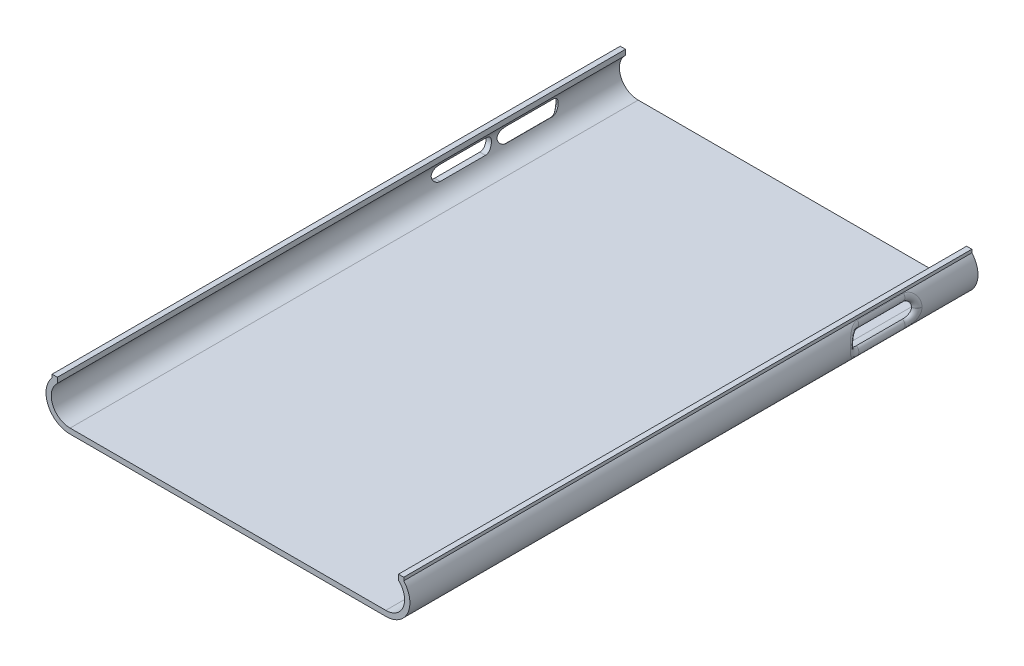
SolidWorks part; units mm, degrees
ref_plane "Front Plane" through (0, 0, 0) normal (0, 0, 1) x (1, 0, 0)
ref_plane "Top Plane" through (0, 0, 0) normal (0, 1, 0) x (1, 0, 0)
ref_plane "Right Plane" through (0, 0, 0) normal (1, 0, 0) x (0, 0, -1)
sketch "Sketch1" plane through (0, 0, 0) normal (0, 0, 1) x (1, 0, 0)
  line L0 (-30, -3.55) -> (30, -3.55)
  line L6 (-29.9932, -4.55) -> (29.9932, -4.55)
  line L13 (32.4171, 2.6) -> (32.4171, 3.6128)
  line L15 (0, 5.8259) -> (0, 4.6128) construction
  line L17 (33.4171, 3.012) -> (33.4171, 3.6128)
  line L19 (-33.4171, 3.012) -> (-33.4171, 3.6128)
  line L20 (-32.4171, 2.6) -> (-32.4171, 3.6128)
  line L21 (-32.4171, 3.6128) -> (-33.4171, 3.6128)
  line L22 (32.4171, 3.6128) -> (33.4171, 3.6128)
  line L23 (0, -3.55) -> (0, -8.435) construction
  line L24 (-33.4171, 4.6128) -> (33.4171, 4.6128) construction
  line L25 (-32.4171, 3.6128) -> (32.4171, 3.6128) construction
  line L26 (33.4171, 3.012) -> (33.4171, 4.6128) construction
  line L27 (-33.4171, 3.012) -> (-33.4171, 4.6128) construction
  arc A1 (-33.4171, 3.012) -> (-29.9932, -4.55) centre (-30.0513, -0.0202) ccw
  arc A4 (33.4171, 3.012) -> (29.9932, -4.55) centre (30.0513, -0.0202) cw
  arc A5 (-32.4171, 2.6) -> (-30, -3.55) centre (-30.0513, -0.0202) ccw
  arc A6 (32.4171, 2.6) -> (30, -3.55) centre (30.0513, -0.0202) cw
  point P9 (0, 0)
  dimension "D1" = 1
extrude "Boss-Extrude1" add sketch "Sketch1" along normal up to vertex (55.95 mm away) and the other way up to vertex (52.03 mm away) from offset 0
sketch "Sketch3" plane through (0, 0, 0) normal (1, 0, 0) x (0, 0, -1)
  line L0 (30.2019, 0) -> (38.9709, 0) construction
  line L1 (30.2019, 1.4186) -> (38.9709, 1.4186)
  line L2 (30.2019, -1.4186) -> (38.9709, -1.4186)
  arc A0 (30.2019, 1.4186) -> (30.2019, -1.4186) centre (30.2019, 0) ccw
  arc A1 (38.9709, -1.4186) -> (38.9709, 1.4186) centre (38.9709, 0) ccw
  point P3 (34.5864, 0)
  point P8 (40.6329, 0)
  point P9 (29.9993, 0)
  point P10 (30.3046, 0)
  point P11 (40.2765, 0)
  point P12 (38.9709, 0)
  point P13 (30.2019, 0)
extrude "Cut-Extrude2" cut sketch "Sketch3" against normal up to surface and the other way up to surface
fillet "Fillet2" radius 1 4 edges at (-34.5789, 0.1321, -28.7895) (-34.5801, -0.1311, -40.3834) (34.5789, 0.1321, -28.7895) (34.5801, -0.1311, -40.3834)
sketch "Sketch4" plane through (0, 0, 0) normal (1, 0, 0) x (0, 0, -1)
  line L0 (30.2019, 0) -> (38.9709, 0) construction
  line L1 (30.2019, 1.4186) -> (38.9709, 1.4186) construction
  line L2 (30.2019, -1.4186) -> (38.9709, -1.4186) construction
  line L3 (30.2019, 0) -> (3.962, 0) construction
  line L4 (17.6803, 0) -> (26.2899, 0) construction
  line L5 (17.6803, 1.4199) -> (26.2899, 1.4199)
  line L6 (17.6803, -1.4199) -> (26.2899, -1.4199)
  arc A0 (30.2019, 1.4186) -> (30.2019, -1.4186) centre (30.2019, 0) ccw construction
  arc A1 (38.9709, -1.4186) -> (38.9709, 1.4186) centre (38.9709, 0) ccw construction
  arc A2 (17.6803, 1.4199) -> (17.6803, -1.4199) centre (17.6803, 0) ccw
  arc A3 (26.2899, -1.4199) -> (26.2899, 1.4199) centre (26.2899, 0) ccw
  point P3 (34.5864, 0)
  point P11 (21.9851, 0)
  point P19 (21.0707, 0)
  point P20 (16.5551, 0)
  point P21 (17.1807, 0)
  point P22 (17.6803, 0)
extrude "Cut-Extrude3" cut sketch "Sketch4" against normal up to surface (34.3465 mm away)
